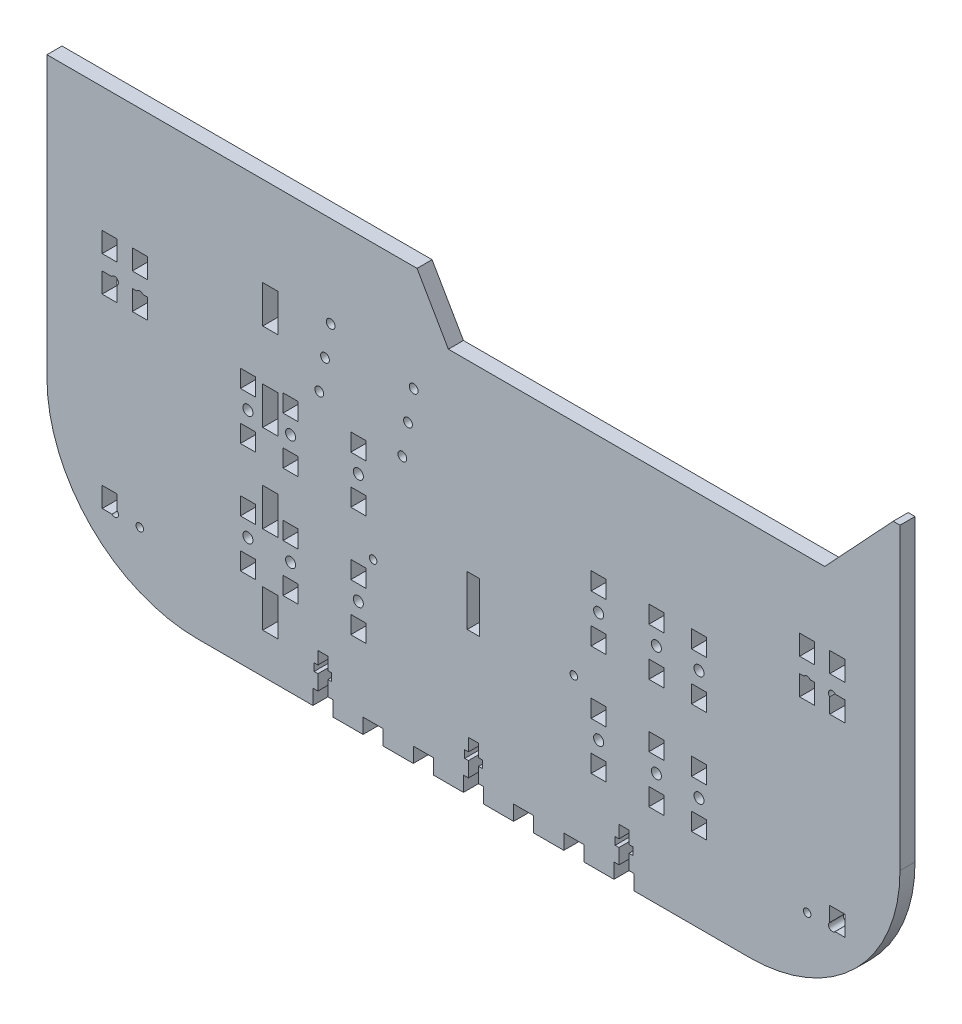
SolidWorks part; units mm, degrees
ref_plane "Plan de face" through (0, 0, 0) normal (0, 0, 1) x (1, 0, 0)
ref_plane "Plan de dessus" through (0, 0, 0) normal (0, 1, 0) x (1, 0, 0)
ref_plane "Plan de droite" through (0, 0, 0) normal (1, 0, 0) x (0, 0, -1)
sketch "Esquisse1" plane through (0, 0, 0) normal (0, 0, 1) x (1, 0, 0)
  line L1 (0, 0) -> (-340, 0)
  line L2 (0, 0) -> (0, 260)
  line L3 (0, 260) -> (-340, 260)
  line L4 (-340, 0) -> (-340, 260)
  line L5 (-340, 0) -> (-340, -49.0561)
  line L6 (0, 0) -> (0, -49.0561)
  point P12 (-170, 0)
  point P13 (-170, 0)
  point P14 (-170, 0)
  dimension "D1" = 340
  dimension "D2" = 260
extrude "Boss.-Extru.1" add sketch "Esquisse1" against normal blind 6
sketch "Esquisse10" plane through (0, 0, -6) normal (0, 0, -1) x (-1, 0, 0)
  line L0 (200.4149, 67) -> (170, 67) construction
  line L1 (170, 67) -> (170, 206.8472) construction
  line L2 (259.9, 58) -> (259.9, 76) construction
  line L3 (262.9, 32) -> (256.9, 32)
  line L4 (262.9, 32) -> (262.9, 39)
  line L5 (262.9, 39) -> (256.9, 39)
  line L6 (256.9, 32) -> (256.9, 39)
  line L7 (262.9, 51) -> (256.9, 51)
  line L8 (262.9, 51) -> (262.9, 58)
  line L9 (262.9, 58) -> (256.9, 58)
  line L10 (256.9, 51) -> (256.9, 58)
  line L11 (262.9, 76) -> (256.9, 76)
  line L12 (262.9, 76) -> (262.9, 83)
  line L13 (262.9, 83) -> (256.9, 83)
  line L14 (256.9, 76) -> (256.9, 83)
  line L15 (262.9, 95) -> (256.9, 95)
  line L16 (262.9, 95) -> (262.9, 102)
  line L17 (262.9, 102) -> (256.9, 102)
  line L18 (256.9, 95) -> (256.9, 102)
  line L19 (245.9, 32) -> (239.9, 32)
  line L20 (172.5, 57) -> (167.5, 57)
  line L21 (172.5, 57) -> (172.5, 77)
  line L22 (172.5, 77) -> (167.5, 77)
  line L23 (167.5, 57) -> (167.5, 77)
  line L24 (245.9, 32) -> (245.9, 39)
  line L25 (245.9, 39) -> (239.9, 39)
  line L26 (239.9, 32) -> (239.9, 39)
  line L27 (245.9, 51) -> (239.9, 51)
  line L28 (245.9, 51) -> (245.9, 58)
  line L29 (245.9, 58) -> (239.9, 58)
  line L30 (239.9, 51) -> (239.9, 58)
  line L31 (245.9, 76) -> (239.9, 76)
  line L32 (245.9, 76) -> (245.9, 83)
  line L33 (245.9, 83) -> (239.9, 83)
  line L34 (239.9, 76) -> (239.9, 83)
  line L35 (245.9, 95) -> (239.9, 95)
  line L36 (245.9, 95) -> (245.9, 102)
  line L37 (245.9, 102) -> (239.9, 102)
  line L38 (239.9, 95) -> (239.9, 102)
  line L39 (215.0613, 88.0489) -> (215.0613, 106.0489) construction
  line L40 (242.9, 58) -> (242.9, 76) construction
  line L41 (242.9, 39) -> (242.9, 51) construction
  line L42 (242.9, 83) -> (242.9, 95) construction
  line L43 (218.9, 32) -> (212.9, 32)
  line L44 (218.9, 32) -> (218.9, 39)
  line L45 (218.9, 39) -> (212.9, 39)
  line L46 (212.9, 32) -> (212.9, 39)
  line L47 (218.9, 51) -> (212.9, 51)
  line L48 (218.9, 51) -> (218.9, 58)
  line L49 (218.9, 58) -> (212.9, 58)
  line L50 (212.9, 51) -> (212.9, 58)
  line L51 (218.9, 76) -> (212.9, 76)
  line L52 (218.9, 76) -> (218.9, 83)
  line L53 (218.9, 83) -> (212.9, 83)
  line L54 (212.9, 76) -> (212.9, 83)
  line L55 (218.9, 95) -> (212.9, 95)
  line L56 (188.0613, 88.0489) -> (188.0613, 106.0489) construction
  line L57 (259.9, 39) -> (259.9, 51) construction
  line L58 (259.9, 83) -> (259.9, 95) construction
  line L59 (100.1, 95) -> (100.1, 102)
  line L60 (94.1, 102) -> (100.1, 102)
  line L61 (94.1, 95) -> (94.1, 102)
  line L62 (94.1, 95) -> (100.1, 95)
  line L63 (100.1, 76) -> (100.1, 83)
  line L64 (94.1, 83) -> (100.1, 83)
  line L65 (94.1, 76) -> (94.1, 83)
  line L66 (94.1, 76) -> (100.1, 76)
  line L67 (100.1, 51) -> (100.1, 58)
  line L68 (94.1, 58) -> (100.1, 58)
  line L69 (94.1, 51) -> (94.1, 58)
  line L70 (94.1, 51) -> (100.1, 51)
  line L71 (100.1, 32) -> (100.1, 39)
  line L72 (94.1, 39) -> (100.1, 39)
  line L73 (94.1, 32) -> (94.1, 39)
  line L74 (94.1, 32) -> (100.1, 32)
  line L75 (83.1, 95) -> (83.1, 102)
  line L76 (77.1, 102) -> (83.1, 102)
  line L77 (77.1, 95) -> (77.1, 102)
  line L78 (77.1, 95) -> (83.1, 95)
  line L79 (83.1, 76) -> (83.1, 83)
  line L80 (77.1, 83) -> (83.1, 83)
  line L81 (77.1, 76) -> (77.1, 83)
  line L82 (77.1, 76) -> (83.1, 76)
  line L83 (187, 67) -> (17, 67) construction
  line L84 (123.1, 95) -> (123.1, 102)
  line L85 (117.1, 102) -> (123.1, 102)
  line L86 (117.1, 95) -> (117.1, 102)
  line L87 (117.1, 95) -> (123.1, 95)
  line L88 (123.1, 76) -> (123.1, 83)
  line L89 (117.1, 83) -> (123.1, 83)
  line L90 (117.1, 76) -> (117.1, 83)
  line L91 (83.1, 51) -> (83.1, 58)
  line L92 (77.1, 58) -> (83.1, 58)
  line L93 (77.1, 51) -> (77.1, 58)
  line L94 (77.1, 51) -> (83.1, 51)
  line L95 (117.1, 76) -> (123.1, 76)
  line L96 (123.1, 51) -> (123.1, 58)
  line L97 (117.1, 58) -> (123.1, 58)
  line L98 (117.1, 51) -> (117.1, 58)
  line L99 (117.1, 51) -> (123.1, 51)
  line L100 (123.1, 32) -> (123.1, 39)
  line L101 (117.1, 39) -> (123.1, 39)
  line L102 (117.1, 32) -> (117.1, 39)
  line L103 (83.1, 32) -> (83.1, 39)
  line L104 (77.1, 39) -> (83.1, 39)
  line L105 (77.1, 32) -> (77.1, 39)
  line L106 (77.1, 32) -> (83.1, 32)
  line L107 (170, 67) -> (0, 67) construction
  line L108 (271.9, 34) -> (292.9, 34)
  line L109 (271.9, 34) -> (271.9, 100)
  line L110 (271.9, 100) -> (292.9, 100)
  line L111 (292.9, 34) -> (292.9, 100)
  line L112 (68.1, 34) -> (47.1, 34)
  line L113 (68.1, 34) -> (68.1, 100)
  line L114 (68.1, 100) -> (47.1, 100)
  line L115 (47.1, 34) -> (47.1, 100)
  line L116 (0, 260) -> (340, 260) construction
  line L118 (47.1, 67) -> (0, 67) construction
  line L119 (292.9, 67) -> (340, 67) construction
  line L121 (117.1, 32) -> (123.1, 32)
  line L122 (210, 67) -> (40, 67) construction
  line L123 (218.9, 95) -> (218.9, 102)
  line L124 (218.9, 102) -> (212.9, 102)
  line L125 (212.9, 95) -> (212.9, 102)
  line L126 (215.9, 58) -> (215.9, 76) construction
  line L127 (215.9, 39) -> (215.9, 51) construction
  line L128 (215.9, 83) -> (215.9, 95) construction
  line L130 (340, 0) -> (340, 260) construction
  circle A0 centre (259.9, 45) radius 2
  circle A1 centre (259.9, 89) radius 2
  circle A2 centre (242.9, 45) radius 2
  circle A3 centre (242.9, 89) radius 2
  circle A4 centre (215.9, 45) radius 2
  circle A5 centre (215.9, 89) radius 2
  circle A6 centre (97.1, 89) radius 2
  circle A7 centre (97.1, 45) radius 2
  circle A8 centre (80.1, 89) radius 2
  circle A9 centre (120.1, 89) radius 2
  circle A10 centre (120.1, 45) radius 2
  circle A11 centre (80.1, 45) radius 2
  point P21 (259.9, 67)
  point P48 (242.9, 67)
  point P144 (292.9, 67)
  point P150 (68.1, 67)
  point P169 (215.9, 67)
  dimension "D14" = 4
  dimension "D15" = 4
  dimension "D1" = 70
  dimension "D2" = 12
  dimension "D3" = 7
  dimension "D4" = 7
  dimension "D5" = 12
  dimension "D6" = 7
  dimension "D7" = 7
  dimension "D8" = 86.9
  dimension "D9" = 6
  dimension "D10" = 2.5
  dimension "D11" = 2.5
  dimension "D12" = 20
  dimension "D13" = 10
  dimension "D16" = 9
  dimension "D17" = 21
  dimension "D18" = 66
  dimension "D19" = 66
  dimension "D20" = 9
  dimension "D21" = 21
  dimension "D22" = 160
  dimension "D23" = 2
  dimension "D27" = 11
  dimension "D28" = 34
  dimension "D29" = 11
  dimension "D30" = 38
  dimension "D24" = 2
  dimension "D25" = 2
  dimension "D26" = 2
extrude "Enlèv. mat.-Extru.5" cut sketch "Esquisse10" against normal blind 6 contours L93 L94 L91 L92 | L81 L82 L79 L80 | L77 L78 L75 L76 | L86 L87 L84 L85 | L102 L121 L100 L101 | L54 L51 L52 L53 | L125 L55 L123 L124 | L46 L43 L44 L45 | L26 L19 L24 L25 | L6 L3 L4 L5 | L10 L7 L8 L9 | L14 L11 L12 L13 | L18 L15 L16 L17 | L105 L104 L103 L106 | L61 L60 L59 L62 | L65 L64 L63 L66 | L90 L89 L88 L95 | L97 L96 L99 L98 | L67 L68 L69 L70 | L72 L71 L74 L73 | A10 | A7 | A11 | A8 | A6 | A9 | L21 L22 L23 L20 | L38 L37 L36 L35 | A5 | A3 | L34 L33 L32 L31 | L30 L29 L28 L27 | L50 L49 L48 L47 | A1 | A0 | A2 | A4
sketch "Esquisse13" plane through (0, 0, -6) normal (0, 0, -1) x (-1, 0, 0)
  line L0 (43, 100) -> (21, 100)
  line L1 (43, 100) -> (43, 96.0745)
  line L2 (43, 34) -> (21, 34)
  line L3 (14, 90) -> (14, 44)
  line L4 (170, 197.2117) -> (170, 30) construction
  line L5 (31.2729, 67.0745) -> (52.2729, 67.0745) construction
  line L6 (297, 38.0745) -> (297, 34)
  line L7 (292.9, 96.0745) -> (292.9, 38.0745)
  line L8 (297, 38.0745) -> (292.9, 38.0745)
  line L9 (297, 96.0745) -> (292.9, 96.0745)
  line L10 (-4.3481, 139.0454) -> (14.1729, 131.4974) construction
  line L11 (56.9221, 195.6452) -> (82.0234, 184.3851) construction
  line L12 (69.2498, 190.1152) -> (170, 190.1152) construction
  line L13 (319, 34) -> (319, 44)
  line L14 (326, 44) -> (319, 44)
  line L15 (319, 100) -> (319, 90)
  line L16 (14, 90) -> (21, 90)
  line L17 (21, 100) -> (21, 90)
  line L18 (326, 90) -> (319, 90)
  line L19 (14, 44) -> (21, 44)
  line L20 (21, 34) -> (21, 44)
  line L21 (43, 96.0745) -> (47.1, 96.0745)
  line L22 (43, 38.0745) -> (47.1, 38.0745)
  line L23 (47.1, 96.0745) -> (47.1, 38.0745)
  line L24 (43, 38.0745) -> (43, 34)
  line L25 (326, 90) -> (326, 44)
  line L26 (297, 34) -> (319, 34)
  line L27 (297, 100) -> (297, 96.0745)
  line L28 (297, 100) -> (319, 100)
  line L29 (32, 34) -> (32, 27) construction
  line L30 (27, 34) -> (37, 34) construction
  line L31 (27, 34) -> (27, 27) construction
  line L32 (27, 27) -> (37, 27) construction
  line L33 (37, 34) -> (37, 27) construction
  line L34 (68.1, 34) -> (68.1, 100) construction
  line L36 (68.1, 100) -> (47.1, 100) construction
  line L37 (47.1, 100) -> (47.1, 34) construction
  line L38 (0, 0) -> (340, 0) construction
  circle A1 centre (69.2498, 190.1152) radius 1.5
  circle A2 centre (119.6249, 190.1152) radius 1.5
  circle A3 centre (220.3751, 190.1152) radius 1.5
  circle A4 centre (270.7502, 190.1152) radius 1.5
  circle A5 centre (27, 27) radius 1.5
  circle A6 centre (130, 62.4) radius 1.5
  circle A7 centre (210, 62.4) radius 1.5
  circle A8 centre (37, 27) radius 1.5
  circle A9 centre (37, 107.1489) radius 1.5
  circle A10 centre (27, 107.1489) radius 1.5
  circle A11 centre (303, 27) radius 1.5
  circle A12 centre (313, 27) radius 1.5
  circle A13 centre (313, 107.1489) radius 1.5
  circle A14 centre (303, 107.1489) radius 1.5
  point P67 (68.1, 67)
  point P68 (14, 67)
  dimension "D3" = 3
  dimension "D6" = 3
  dimension "D7" = 3
  dimension "D16" = 3
  dimension "D17" = 3
  dimension "D1" = 66
  dimension "D4" = 3.9255
  dimension "D5" = 14
  dimension "D8" = 40
  dimension "D9" = 32.4
  dimension "D10" = 7
  dimension "D11" = 10
  dimension "D12" = 10
  dimension "D13" = 22
  dimension "D14" = 7
  dimension "D15" = 10
  dimension "D18" = 33.1
  dimension "D19" = 4.0745
  dimension "D20" = 22.1498
  dimension "D21" = 82.9
  dimension "D22" = 7.1489
  dimension "D23" = 30
extrude "Enlèv. mat.-Extru.6" cut sketch "Esquisse13" against normal blind 6 contours A8 | A5 | A9 | A10 | A6 | A7 | A12 | A11 | A13 | A14
fillet "Congé1" radius 60 2 edges at (0, 0, -3) (-340, 0, -3)
sketch "Esquisse14" plane through (0, 0, -6) normal (0, 0, -1) x (-1, 0, 0)
  line L0 (0, 260) -> (340, 260) construction
  line L1 (145, 260) -> (325, 260)
  line L2 (145, 260) -> (145, 250)
  line L3 (145, 250) -> (325, 250)
  line L4 (325, 260) -> (325, 250)
  line L6 (340, 60) -> (340, 260) construction
  dimension "D1" = 10
  dimension "D2" = 180
  dimension "D3" = 15
extrude "Enlèv. mat.-Extru.7" cut sketch "Esquisse14" against normal blind 10
sketch "Esquisse15" plane through (0, 0, 0) normal (0, 0, 1) x (1, 0, 0)
  line L0 (-325, 250) -> (-145, 250) construction
  line L1 (-310, 250) -> (-190, 250)
  line L2 (-310, 250) -> (-310, 248)
  line L3 (-310, 248) -> (-190, 248)
  line L4 (-190, 250) -> (-190, 248)
  line L5 (-340, 60) -> (-340, 260) construction
  dimension "D1" = 30
  dimension "D2" = 120
  dimension "D3" = 2
extrude "Enlèv. mat.-Extru.8" cut sketch "Esquisse15" against normal blind 10
fillet "Congé2" radius 10 2 edges at (-190, 250, -3) (-310, 250, -3)
fillet "Congé3" radius 8 2 edges at (-145, 260, -3) (-325, 260, -3)
sketch "Esquisse16" plane through (0, 0, 0) normal (0, 0, 1) x (1, 0, 0)
  line L1 (-340, 60) -> (-340, 260) construction
  line L2 (-60, 0) -> (-280, 0) construction
  line L4 (-231.45, 109.66) -> (-226.93, 135.27)
  line L5 (-198.36, 103.83) -> (-193.84, 129.44)
  circle A6 centre (-231.45, 109.66) radius 1.75
  circle A7 centre (-226.93, 135.27) radius 1.75
  circle A8 centre (-229.19, 122.465) radius 1.75
  circle A9 centre (-198.36, 103.83) radius 1.75
  circle A10 centre (-198.36, 103.83) radius 1.75
  circle A11 centre (-193.84, 129.44) radius 1.75
  circle A12 centre (-196.1, 116.635) radius 1.75
  dimension "D14" = 3.5
  dimension "D19" = 3.5
  dimension "D20" = 3.5
  dimension "D23" = 3.5
  dimension "D25" = 3.5
  dimension "D26" = 3.5
  dimension "D15" = 108.55
  dimension "D16" = 109.66
  dimension "D17" = 113.07
  dimension "D18" = 135.27
  dimension "D21" = 141.64
  dimension "D22" = 103.83
  dimension "D24" = 26.0058
  dimension "D27" = 33.5997
extrude "Enlèv. mat.-Extru.9" cut sketch "Esquisse16" against normal blind 6 contours A9 | A12 | A11 | A8 | A6 | A7
sketch "Esquisse17" plane through (0, 0, 0) normal (0, 0, 1) x (1, 0, 0)
  line L0 (-30, 150) -> (-140, 150)
  line L1 (-25.8174, 254.8022) -> (-23.4785, 247.1518)
  line L2 (-25.8174, 254.8022) -> (-31.5553, 253.048)
  line L3 (0, 260) -> (-137, 260) construction
  line L4 (0, 60) -> (0, 260) construction
  line L5 (-30, 150) -> (-2.7201, 179.2541)
  line L6 (-2.7201, 179.2541) -> (-34.881, 284.4477)
  line L7 (-140, 150) -> (-180, 150)
  line L8 (-180, 150) -> (-205, 193.3013)
  line L9 (-205, 193.3013) -> (-102.154, 315.8684)
  line L10 (-2.7201, 179.2541) -> (-102.154, 315.8684)
  line L11 (-31.6649, 273.9283) -> (-29.3259, 266.2779)
  line L12 (-31.6649, 273.9283) -> (-37.4027, 272.1741)
  line L13 (-29.3259, 266.2779) -> (-35.0637, 264.5237)
  line L14 (-37.4027, 272.1741) -> (-35.0637, 264.5237)
  line L15 (-23.4785, 247.1518) -> (-29.2163, 245.3976)
  line L16 (-31.5553, 253.048) -> (-29.2163, 245.3976)
  line L17 (-19.97, 235.6761) -> (-17.631, 228.0257)
  line L18 (-19.97, 235.6761) -> (-25.7078, 233.9219)
  line L19 (-17.631, 228.0257) -> (-23.3689, 226.2715)
  line L20 (-25.7078, 233.9219) -> (-23.3689, 226.2715)
  line L21 (-14.1226, 216.55) -> (-11.7836, 208.8996)
  line L22 (-14.1226, 216.55) -> (-19.8604, 214.7958)
  line L23 (-11.7836, 208.8996) -> (-17.5214, 207.1454)
  line L24 (-19.8604, 214.7958) -> (-17.5214, 207.1454)
  line L25 (-5.9362, 189.7735) -> (-8.2751, 197.4239)
  line L26 (-5.9362, 189.7735) -> (-11.674, 188.0193)
  line L27 (-8.2751, 197.4239) -> (-14.013, 195.6697)
  line L28 (-11.674, 188.0193) -> (-14.013, 195.6697)
  dimension "D1" = 110
  dimension "D2" = 110
  dimension "D3" = 140
  dimension "D4" = 133
  dimension "D5" = 40
  dimension "D6" = 110
  dimension "D7" = 120
  dimension "D8" = 50
  dimension "D9" = 40
  dimension "D10" = 120
  dimension "D11" = 110
  dimension "D12" = 160
  dimension "D13" = 6
  dimension "D14" = 8
  dimension "D15" = 11
  dimension "D16" = 12
  dimension "D17" = 12
  dimension "D18" = 12
  dimension "D19" = 12
extrude "Enlèv. mat.-Extru.10" cut sketch "Esquisse17" against normal blind 10 contours L26 L28 L10 L9 L8 L7 L0 L5 | L21 L23 L24 L22 | L11 L13 L14 L12 | L1 L15 L16 L2 | L17 L19 L20 L18
sketch "Esquisse18" plane through (0, 0, 0) normal (0, 0, 1) x (1, 0, 0)
  line L0 (-60, 0) -> (-280, 0) construction
  line L1 (-106, 0) -> (-114, 0)
  line L2 (-106, 0) -> (-106, 6)
  line L3 (-106, 6) -> (-114, 6)
  line L4 (-114, 0) -> (-114, 6)
  line L6 (-126, 0) -> (-134, 0)
  line L7 (-126, 0) -> (-126, 6)
  line L8 (-126, 6) -> (-134, 6)
  line L9 (-134, 0) -> (-134, 6)
  line L10 (-146, 0) -> (-154, 0)
  line L11 (-146, 0) -> (-146, 6)
  line L12 (-146, 6) -> (-154, 6)
  line L13 (-154, 0) -> (-154, 6)
  line L14 (-166, 0) -> (-174, 0)
  line L15 (-166, 0) -> (-166, 6)
  line L16 (-166, 6) -> (-174, 6)
  line L17 (-174, 0) -> (-174, 6)
  line L18 (-186, 0) -> (-194, 0)
  line L19 (-186, 0) -> (-186, 6)
  line L20 (-186, 6) -> (-194, 6)
  line L21 (-194, 0) -> (-194, 6)
  line L22 (-206, 0) -> (-214, 0)
  line L23 (-206, 0) -> (-206, 6)
  line L24 (-206, 6) -> (-214, 6)
  line L25 (-214, 0) -> (-214, 6)
  line L26 (-226, 0) -> (-234, 0)
  line L27 (-226, 0) -> (-226, 6)
  line L28 (-226, 6) -> (-234, 6)
  line L29 (-234, 0) -> (-234, 6)
  point P30 (-170, 0)
  point P31 (-170, 0)
  dimension "D1" = 6
  dimension "D2" = 8
  dimension "D3" = 12
  dimension "D4" = 12
  dimension "D5" = 12
  dimension "D6" = 12
  dimension "D7" = 12
  dimension "D8" = 12
extrude "Enlèv. mat.-Extru.11" cut sketch "Esquisse18" against normal blind 10
sketch "Esquisse19" plane through (0, 0, 0) normal (0, 0, 1) x (1, 0, 0)
  line L0 (-61.4905, 260) -> (-2.7201, 179.2541)
  line L1 (-2.7201, 179.2541) -> (0, 179.2541)
  line L2 (0, 260) -> (-61.4905, 260) construction
  line L3 (-27.4065, 260) -> (0, 260)
  line L4 (0, 60) -> (0, 260) construction
  line L5 (0, 260) -> (0, 193.1641)
  line L6 (0, 179.2541) -> (0, 260)
extrude "Enlèv. mat.-Extru.13" cut sketch "Esquisse19" against normal blind 6 contours L0 L1 L6
sketch "Esquisse20" plane through (0, 0, 0) normal (0, 0, 1) x (1, 0, 0)
  line L0 (-192.5, 171.6506) -> (-340, 171.6506)
  line L1 (-180, 150) -> (-205, 193.3013) construction
  line L2 (-340, 60) -> (-340, 260) construction
  line L3 (-192.5, 171.6506) -> (-157.4241, 250)
  line L4 (-157.4241, 250) -> (-157.4241, 260.6427)
  line L5 (-157.4241, 260.6427) -> (-340, 260)
  line L6 (-340, 260) -> (-340, 171.6506)
extrude "Enlèv. mat.-Extru.14" cut sketch "Esquisse20" against normal blind 10
sketch "Esquisse21" plane through (0, 0, 0) normal (0, 0, 1) x (1, 0, 0)
  line L0 (-312, 26) -> (-312, 34) construction
  line L1 (-306, 122) -> (-300, 122)
  line L2 (-306, 122) -> (-306, 114)
  line L3 (-306, 114) -> (-300, 114)
  line L4 (-300, 122) -> (-300, 114)
  line L5 (-312, 122) -> (-318, 122)
  line L6 (-312, 122) -> (-312, 114)
  line L7 (-312, 114) -> (-318, 114)
  line L8 (-318, 122) -> (-318, 114)
  line L9 (-318, 108) -> (-312, 108)
  line L10 (-318, 108) -> (-318, 100)
  line L11 (-318, 100) -> (-312, 100)
  line L12 (-312, 108) -> (-312, 100)
  line L13 (-306, 108) -> (-300, 108)
  line L14 (-306, 108) -> (-306, 100)
  line L15 (-306, 100) -> (-300, 100)
  line L16 (-300, 108) -> (-300, 100)
  line L17 (-318, 34) -> (-312, 34)
  line L18 (-318, 34) -> (-318, 26)
  line L19 (-318, 26) -> (-312, 26)
  line L20 (-312, 34) -> (-312, 26)
  line L21 (-318, 26) -> (-312, 26) construction
  line L27 (-28, 34) -> (-22, 34)
  line L28 (-28, 34) -> (-28, 26)
  line L29 (-28, 26) -> (-22, 26)
  line L30 (-22, 34) -> (-22, 26)
  line L35 (-34, 100) -> (-40, 100)
  line L36 (-34, 100) -> (-34, 108)
  line L37 (-34, 108) -> (-40, 108)
  line L38 (-40, 100) -> (-40, 108)
  line L39 (-40, 122) -> (-34, 122)
  line L40 (-40, 122) -> (-40, 114)
  line L41 (-40, 114) -> (-34, 114)
  line L42 (-34, 122) -> (-34, 114)
  line L43 (-22, 108) -> (-28, 108)
  line L44 (-22, 108) -> (-22, 100)
  line L45 (-22, 100) -> (-28, 100)
  line L46 (-28, 108) -> (-28, 100)
  line L47 (-22, 114) -> (-28, 114)
  line L48 (-22, 114) -> (-22, 122)
  line L49 (-22, 122) -> (-28, 122)
  line L50 (-28, 114) -> (-28, 122)
extrude "Enlèv. mat.-Extru.15" cut sketch "Esquisse21" against normal blind 10
sketch "Esquisse22" plane through (0, 0, -6) normal (0, 0, -1) x (-1, 0, 0)
  line L1 (248, 136) -> (254, 136)
  line L2 (248, 136) -> (248, 121)
  line L3 (248, 121) -> (254, 121)
  line L4 (254, 136) -> (254, 121)
  line L5 (248, 101) -> (254, 101)
  line L6 (248, 101) -> (248, 86)
  line L7 (248, 86) -> (254, 86)
  line L8 (254, 101) -> (254, 86)
  line L9 (248, 66) -> (254, 66)
  line L10 (248, 66) -> (248, 51)
  line L11 (248, 51) -> (254, 51)
  line L12 (254, 66) -> (254, 51)
  line L13 (248, 16) -> (254, 16)
  line L14 (248, 16) -> (248, 31)
  line L15 (248, 31) -> (254, 31)
  line L16 (254, 16) -> (254, 31)
extrude "Enlèv. mat.-Extru.16" cut sketch "Esquisse22" against normal blind 6
sketch "Esquisse23" plane through (0, 0, -6) normal (0, 0, -1) x (-1, 0, 0)
  line L0 (106, 6) -> (114, 6) construction
  line L1 (112, 6) -> (108, 6)
  line L2 (112, 6) -> (112, 20)
  line L3 (112, 20) -> (108, 20)
  line L4 (108, 6) -> (108, 20)
  line L5 (106, 0) -> (106, 6) construction
  line L6 (113.5, 12) -> (106.5, 12)
  line L7 (113.5, 12) -> (113.5, 15)
  line L8 (113.5, 15) -> (106.5, 15)
  line L9 (106.5, 12) -> (106.5, 15)
  line L10 (126, 6) -> (114, 6) construction
  line L11 (126.256, 232.2411) -> (122.256, 232.2411)
  line L12 (126.256, 232.2411) -> (126.256, 246.2411)
  line L13 (126.256, 246.2411) -> (122.256, 246.2411)
  line L14 (122.256, 232.2411) -> (122.256, 246.2411)
  line L15 (127.756, 238.2411) -> (120.756, 238.2411)
  line L16 (127.756, 238.2411) -> (127.756, 241.2411)
  line L17 (127.756, 241.2411) -> (120.756, 241.2411)
  line L18 (120.756, 238.2411) -> (120.756, 241.2411)
  line L19 (172, 6) -> (168, 6)
  line L20 (172, 6) -> (172, 20)
  line L21 (172, 20) -> (168, 20)
  line L22 (168, 6) -> (168, 20)
  line L23 (173.5, 12) -> (166.5, 12)
  line L24 (173.5, 12) -> (173.5, 15)
  line L25 (173.5, 15) -> (166.5, 15)
  line L26 (166.5, 12) -> (166.5, 15)
  line L27 (166, 6) -> (174, 6) construction
  line L28 (166, 0) -> (166, 6) construction
  line L29 (251.731, 183.3316) -> (247.731, 183.3316)
  line L30 (251.731, 183.3316) -> (251.731, 197.3316)
  line L31 (251.731, 197.3316) -> (247.731, 197.3316)
  line L32 (247.731, 183.3316) -> (247.731, 197.3316)
  line L33 (253.231, 189.3316) -> (246.231, 189.3316)
  line L34 (253.231, 189.3316) -> (253.231, 192.3316)
  line L35 (253.231, 192.3316) -> (246.231, 192.3316)
  line L36 (246.231, 189.3316) -> (246.231, 192.3316)
  line L37 (232, 6) -> (228, 6)
  line L38 (232, 6) -> (232, 20)
  line L39 (232, 20) -> (228, 20)
  line L40 (228, 6) -> (228, 20)
  line L41 (233.5, 12) -> (226.5, 12)
  line L42 (233.5, 12) -> (233.5, 15)
  line L43 (233.5, 15) -> (226.5, 15)
  line L44 (226.5, 12) -> (226.5, 15)
  line L45 (226, 6) -> (234, 6) construction
  line L46 (226, 0) -> (226, 6) construction
  dimension "D1" = 4
  dimension "D2" = 2
  dimension "D3" = 14
  dimension "D4" = 6
  dimension "D5" = 3
  dimension "D6" = 7
  dimension "D7" = 1.5
  dimension "D8" = 4
  dimension "D9" = 14
  dimension "D10" = 3
  dimension "D11" = 7
  dimension "D12" = 1.5
  dimension "D13" = 4
  dimension "D14" = 14
  dimension "D15" = 3
  dimension "D16" = 7
  dimension "D17" = 1.5
  dimension "D18" = 2
  dimension "D19" = 6
  dimension "D20" = 4
  dimension "D21" = 14
  dimension "D22" = 3
  dimension "D23" = 7
  dimension "D24" = 1.5
  dimension "D25" = 6
  dimension "D26" = 4
  dimension "D27" = 14
  dimension "D28" = 3
  dimension "D29" = 7
  dimension "D30" = 1.5
  dimension "D31" = 6
  dimension "D32" = 2
extrude "Enlèv. mat.-Extru.17" cut sketch "Esquisse23" against normal through all contours L38 L41 L40 L37 | L22 L21 L20 L19 | L25 L26 L23 L24 | L4 L3 L2 L1 | L8 L9 L6 L7
